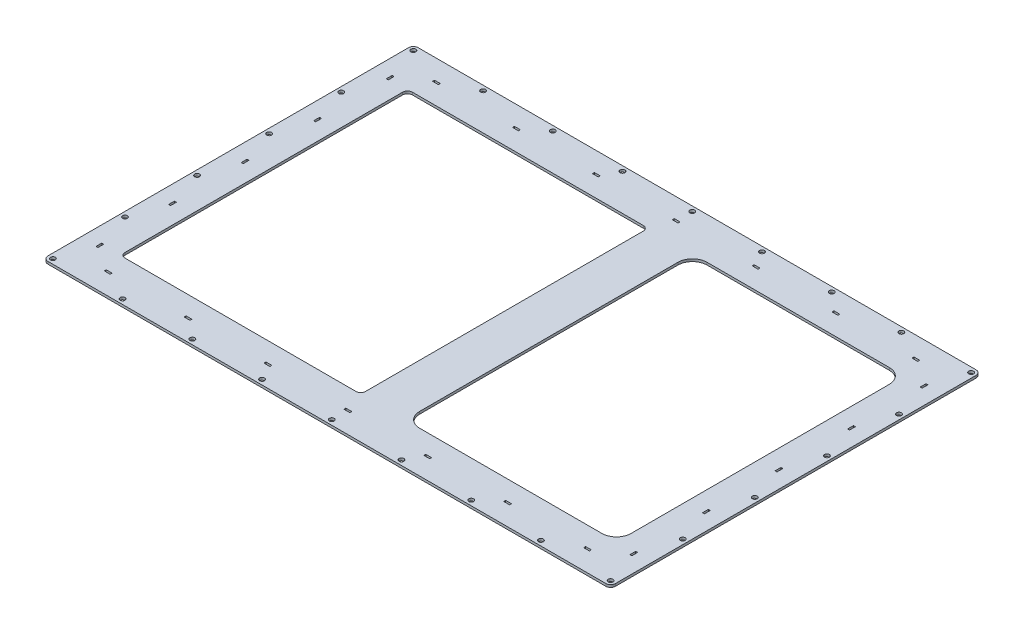
SolidWorks part; units mm, degrees
ref_plane "Спереди" through (0, 0, 0) normal (0, 0, 1) x (1, 0, 0)
ref_plane "Сверху" through (0, 0, 0) normal (0, 1, 0) x (1, 0, 0)
ref_plane "Справа" through (0, 0, 0) normal (1, 0, 0) x (0, 0, -1)
sketch "Эскиз1" plane through (0, 0, 0) normal (0, 1, 0) x (1, 0, 0)
  line L1 (-582.5, -380) -> (582.5, -380)
  line L2 (-582.5, -380) -> (-582.5, 380)
  line L3 (-582.5, 380) -> (582.5, 380)
  line L4 (582.5, -380) -> (582.5, 380)
  line L5 (0, 380) -> (0, -380) construction
  line L6 (-582.5, 0) -> (582.5, 0) construction
  line L7 (-509.5, 295) -> (-15.5, 295)
  line L8 (-509.5, 295) -> (-509.5, -295)
  line L9 (-509.5, -295) -> (-15.5, -295)
  line L10 (-15.5, 295) -> (-15.5, -295)
  line L11 (75.5, 295) -> (509.5, 295)
  line L12 (75.5, 295) -> (75.5, -295)
  line L13 (75.5, -295) -> (509.5, -295)
  line L14 (509.5, 295) -> (509.5, -295)
  point P0 (0, 0)
  dimension "D1" = 1165
  dimension "D2" = 760
  dimension "D3" = 73
  dimension "D4" = 85
  dimension "D5" = 85
  dimension "D6" = 494
  dimension "D7" = 73
  dimension "D8" = 434
extrude "Бобышка-Вытянуть1" add sketch "Эскиз1" along normal mid plane 5
fillet "Скругление1" radius 10 8 edges at (582.5, 0, 380) (-582.5, 0, 380) (582.5, 0, -380) (-582.5, 0, -380) (-15.5, 0, 295) (-509.5, 0, 295) (-15.5, 0, -295) (-509.5, 0, -295)
fillet "Скругление2" radius 30 4 edges at (75.5, 0, 295) (509.5, 0, 295) (509.5, 0, -295) (75.5, 0, -295)
sketch "Эскиз2" plane through (0, 2.5, 0) normal (0, 1, 0) x (1, 0, 0)
  circle A0 centre (-572.5, -370) radius 5
  arc A1 (-582.5, -370) -> (-572.5, -380) centre (-572.5, -370) ccw construction
  circle A2 centre (-572.5, 370) radius 5 construction
  arc A3 (-572.5, 380) -> (-582.5, 370) centre (-572.5, 370) ccw construction
  circle A4 centre (572.5, -370) radius 5 construction
  arc A5 (572.5, -380) -> (582.5, -370) centre (572.5, -370) ccw construction
  point P11 (-572.5, 370)
  point P17 (572.5, -370)
  dimension "D1" = 10
extrude "Вырез-Вытянуть1" cut sketch "Эскиз2" against normal through all
ref_plane "Плоскость1" through (30, 0, 0) normal (-1, 0, 0) x (0, 0, 1)
pattern_linear "Линейный массив1" count 6 spacing 148 along (0, 0, -1) count 9 spacing 143.125 along (1, 0, 0) skipping (1, 1), (1, 2), (1, 3), (1, 4), (1, 5), (1, 6), (1, 7), (2, 1), (2, 2), (2, 3), (2, 4), (2, 5), (2, 6), (2, 7), (3, 1), (3, 2), (3, 3), (3, 4), (3, 5), (3, 6), (3, 7), (4, 1), (4, 2), (4, 3), (4, 4) of "Вырез-Вытянуть1"
sketch "Эскиз3" plane through (0, 2.5, 0) normal (0, 1, 0) x (1, 0, 0)
  line L4 (486, 335) -> (498, 335)
  line L5 (486, 339) -> (486, 335)
  line L6 (498, 339) -> (486, 339)
  line L7 (498, 335) -> (498, 339)
  line L8 (486, 335) -> (498, 335)
  line L9 (486, 339) -> (486, 335)
  line L10 (498, 339) -> (486, 339)
  line L11 (498, 335) -> (498, 339)
  line L12 (322, 335) -> (334, 335)
  line L13 (322, 339) -> (322, 335)
  line L14 (334, 339) -> (322, 339)
  line L15 (334, 335) -> (334, 339)
  line L16 (322, 335) -> (334, 335)
  line L17 (322, 339) -> (322, 335)
  line L18 (334, 339) -> (322, 339)
  line L19 (334, 335) -> (334, 339)
  line L20 (6, 339) -> (-6, 339)
  line L21 (6, 335) -> (6, 339)
  line L22 (-6, 335) -> (6, 335)
  line L23 (-6, 339) -> (-6, 335)
  line L24 (6, 339) -> (-6, 339)
  line L25 (6, 335) -> (6, 339)
  line L26 (-6, 335) -> (6, 335)
  line L27 (-6, 339) -> (-6, 335)
  line L28 (170, 339) -> (158, 339)
  line L29 (158, 339) -> (158, 335)
  line L30 (158, 335) -> (170, 335)
  line L31 (170, 335) -> (170, 339)
  line L32 (170, 339) -> (158, 339)
  line L33 (158, 339) -> (158, 335)
  line L34 (158, 335) -> (170, 335)
  line L35 (170, 335) -> (170, 339)
  line L36 (-498, 335) -> (-486, 335)
  line L37 (-498, 339) -> (-498, 335)
  line L38 (-486, 339) -> (-498, 339)
  line L39 (-486, 335) -> (-486, 339)
  line L40 (-498, 335) -> (-486, 335)
  line L41 (-498, 339) -> (-498, 335)
  line L42 (-486, 339) -> (-498, 339)
  line L43 (-486, 335) -> (-486, 339)
  line L44 (-170, 335) -> (-158, 335)
  line L45 (-170, 339) -> (-170, 335)
  line L46 (-158, 339) -> (-170, 339)
  line L47 (-158, 335) -> (-158, 339)
  line L48 (-170, 335) -> (-158, 335)
  line L49 (-170, 339) -> (-170, 335)
  line L50 (-158, 339) -> (-170, 339)
  line L51 (-158, 335) -> (-158, 339)
  line L52 (-334, 335) -> (-322, 335)
  line L53 (-334, 339) -> (-334, 335)
  line L54 (-322, 339) -> (-334, 339)
  line L55 (-322, 335) -> (-322, 339)
  line L56 (-334, 335) -> (-322, 335)
  line L57 (-334, 339) -> (-334, 335)
  line L58 (-322, 339) -> (-334, 339)
  line L59 (-322, 335) -> (-322, 339)
  line L60 (486, -339) -> (498, -339)
  line L61 (486, -335) -> (486, -339)
  line L62 (498, -335) -> (486, -335)
  line L63 (498, -339) -> (498, -335)
  line L64 (486, -339) -> (498, -339)
  line L65 (486, -335) -> (486, -339)
  line L66 (498, -335) -> (486, -335)
  line L67 (498, -339) -> (498, -335)
  line L68 (322, -339) -> (334, -339)
  line L69 (322, -335) -> (322, -339)
  line L70 (334, -335) -> (322, -335)
  line L71 (334, -339) -> (334, -335)
  line L72 (322, -339) -> (334, -339)
  line L73 (322, -335) -> (322, -339)
  line L74 (334, -335) -> (322, -335)
  line L75 (334, -339) -> (334, -335)
  line L76 (6, -335) -> (-6, -335)
  line L77 (6, -339) -> (6, -335)
  line L78 (-6, -339) -> (6, -339)
  line L79 (-6, -335) -> (-6, -339)
  line L80 (6, -335) -> (-6, -335)
  line L81 (6, -339) -> (6, -335)
  line L82 (-6, -339) -> (6, -339)
  line L83 (-6, -335) -> (-6, -339)
  line L84 (170, -335) -> (158, -335)
  line L85 (158, -335) -> (158, -339)
  line L86 (158, -339) -> (170, -339)
  line L87 (170, -339) -> (170, -335)
  line L88 (170, -335) -> (158, -335)
  line L89 (158, -335) -> (158, -339)
  line L90 (158, -339) -> (170, -339)
  line L91 (170, -339) -> (170, -335)
  line L92 (-498, -339) -> (-486, -339)
  line L93 (-498, -335) -> (-498, -339)
  line L94 (-486, -335) -> (-498, -335)
  line L95 (-486, -339) -> (-486, -335)
  line L96 (-498, -339) -> (-486, -339)
  line L97 (-498, -335) -> (-498, -339)
  line L98 (-486, -335) -> (-498, -335)
  line L99 (-486, -339) -> (-486, -335)
  line L100 (-170, -339) -> (-158, -339)
  line L101 (-170, -335) -> (-170, -339)
  line L102 (-158, -335) -> (-170, -335)
  line L103 (-158, -339) -> (-158, -335)
  line L104 (-170, -339) -> (-158, -339)
  line L105 (-170, -335) -> (-170, -339)
  line L106 (-158, -335) -> (-170, -335)
  line L107 (-158, -339) -> (-158, -335)
  line L108 (-334, -339) -> (-322, -339)
  line L109 (-334, -335) -> (-334, -339)
  line L110 (-322, -335) -> (-334, -335)
  line L111 (-322, -339) -> (-322, -335)
  line L112 (-334, -339) -> (-322, -339)
  line L113 (-334, -335) -> (-334, -339)
  line L114 (-322, -335) -> (-334, -335)
  line L115 (-322, -339) -> (-322, -335)
  line L116 (-546, 143) -> (-546, 155)
  line L117 (-550, 143) -> (-546, 143)
  line L118 (-550, 155) -> (-550, 143)
  line L119 (-546, 155) -> (-550, 155)
  line L120 (-546, 143) -> (-546, 155)
  line L121 (-550, 143) -> (-546, 143)
  line L122 (-550, 155) -> (-550, 143)
  line L123 (-546, 155) -> (-550, 155)
  line L124 (-550, 304) -> (-550, 292)
  line L125 (-546, 304) -> (-550, 304)
  line L126 (-546, 292) -> (-546, 304)
  line L127 (-550, 292) -> (-546, 292)
  line L128 (-550, 304) -> (-550, 292)
  line L129 (-546, 304) -> (-550, 304)
  line L130 (-546, 292) -> (-546, 304)
  line L131 (-550, 292) -> (-546, 292)
  line L132 (-550, -143) -> (-550, -155)
  line L133 (-546, -143) -> (-550, -143)
  line L134 (-546, -155) -> (-546, -143)
  line L135 (-550, -155) -> (-546, -155)
  line L136 (-550, -143) -> (-550, -155)
  line L137 (-546, -143) -> (-550, -143)
  line L138 (-546, -155) -> (-546, -143)
  line L139 (-550, -155) -> (-546, -155)
  line L140 (-550, 6) -> (-550, -6)
  line L141 (-546, 6) -> (-550, 6)
  line L142 (-546, -6) -> (-546, 6)
  line L143 (-550, -6) -> (-546, -6)
  line L144 (-550, 6) -> (-550, -6)
  line L145 (-546, 6) -> (-550, 6)
  line L146 (-546, -6) -> (-546, 6)
  line L147 (-550, -6) -> (-546, -6)
  line L148 (-550, -292) -> (-550, -304)
  line L149 (-546, -292) -> (-550, -292)
  line L150 (-546, -304) -> (-546, -292)
  line L151 (-550, -304) -> (-546, -304)
  line L152 (-550, -292) -> (-550, -304)
  line L153 (-546, -292) -> (-550, -292)
  line L154 (-546, -304) -> (-546, -292)
  line L155 (-550, -304) -> (-546, -304)
  line L176 (546, -143) -> (546, -155)
  line L177 (550, -143) -> (546, -143)
  line L178 (550, -155) -> (550, -143)
  line L179 (546, -155) -> (550, -155)
  line L180 (546, -143) -> (546, -155)
  line L181 (550, -143) -> (546, -143)
  line L182 (550, -155) -> (550, -143)
  line L183 (546, -155) -> (550, -155)
  line L184 (550, -304) -> (550, -292)
  line L185 (546, -304) -> (550, -304)
  line L186 (546, -292) -> (546, -304)
  line L187 (550, -292) -> (546, -292)
  line L188 (550, -304) -> (550, -292)
  line L189 (546, -304) -> (550, -304)
  line L190 (546, -292) -> (546, -304)
  line L191 (550, -292) -> (546, -292)
  line L192 (550, 143) -> (550, 155)
  line L193 (546, 143) -> (550, 143)
  line L194 (546, 155) -> (546, 143)
  line L195 (550, 155) -> (546, 155)
  line L196 (550, 143) -> (550, 155)
  line L197 (546, 143) -> (550, 143)
  line L198 (546, 155) -> (546, 143)
  line L199 (550, 155) -> (546, 155)
  line L200 (550, -6) -> (550, 6)
  line L201 (546, -6) -> (550, -6)
  line L202 (546, 6) -> (546, -6)
  line L203 (550, 6) -> (546, 6)
  line L204 (550, -6) -> (550, 6)
  line L205 (546, -6) -> (550, -6)
  line L206 (546, 6) -> (546, -6)
  line L207 (550, 6) -> (546, 6)
  line L208 (550, 292) -> (550, 304)
  line L209 (546, 292) -> (550, 292)
  line L210 (546, 304) -> (546, 292)
  line L211 (550, 304) -> (546, 304)
  line L212 (550, 292) -> (550, 304)
  line L213 (546, 292) -> (550, 292)
  line L214 (546, 304) -> (546, 292)
  line L215 (550, 304) -> (546, 304)
  dimension "D1" = 0
  dimension "D2" = 0
  dimension "D3" = 0
  dimension "D4" = 0
  dimension "D5" = 0
  dimension "D6" = 0
  dimension "D7" = 0
  dimension "D8" = 0
  dimension "D9" = 0
  dimension "D10" = 0
  dimension "D11" = 0
  dimension "D12" = 0
  dimension "D13" = 0
  dimension "D14" = 0
  dimension "D15" = 0
  dimension "D16" = 0
  dimension "D17" = 0
  dimension "D18" = 0
  dimension "D19" = 0
  dimension "D20" = 0
  dimension "D21" = 0
  dimension "D22" = 0
  dimension "D23" = 0
  dimension "D24" = 0
extrude "Вырез-Вытянуть2" cut sketch "Эскиз3" against normal through all
